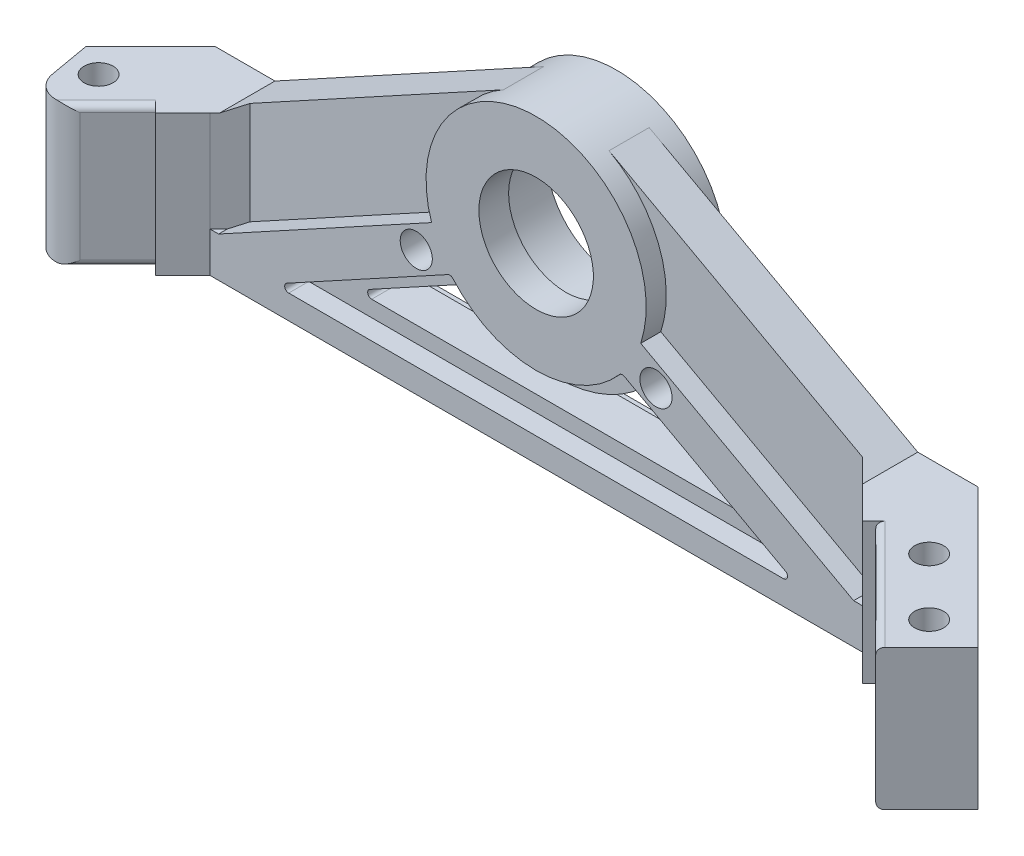
SolidWorks part; units mm, degrees
note: The reader was unsure of these and kept them because the rebuilt part matched: shared geometry of "Sketch2<3>", "Sketch2<5>", "Sketch5<3>".
ref_plane "Front Plane" through (0, 0, 0) normal (0, 0, 1) x (1, 0, 0)
ref_plane "Top Plane" through (0, 0, 0) normal (0, 1, 0) x (1, 0, 0)
ref_plane "Right Plane" through (0, 0, 0) normal (1, 0, 0) x (0, 0, -1)
sketch "Sketch1" plane through (0, 0, 0) normal (0, 1, 0) x (-1, 0, 0)
  line L48 (74.9309, 32.5085) -> (74.2125, 33.2269)
  line L49 (74.2125, 33.2269) -> (56.9345, 15.9489)
  line L50 (57.6529, 15.2305) -> (56.9345, 15.9489)
  line L51 (-56.9345, 15.9489) -> (-74.2125, 33.2269)
  line L52 (-74.2125, 33.2269) -> (-74.9309, 32.5085)
  line L53 (-56.9345, 15.9489) -> (-57.6529, 15.2305)
  line L54 (-65.0167, 7.8667) -> (-61.5144, 4.3644)
  line L55 (-61.5144, 4.3644) -> (-52.3715, 13.5073)
  line L56 (-52.3715, 13.5073) -> (-55.8738, 17.0096)
  line L57 (-55.8738, 17.0096) -> (-65.0167, 7.8667)
  line L58 (55.8738, 17.0096) -> (52.3715, 13.5073)
  line L59 (52.3715, 13.5073) -> (61.5144, 4.3644)
  line L60 (61.5144, 4.3644) -> (65.0167, 7.8667)
  line L61 (65.0167, 7.8667) -> (55.8738, 17.0096)
  line L62 (17.3112, 9.525) -> (13.6482, 9.525)
  line L63 (17.3112, 12.7) -> (-17.3112, 12.7)
  line L64 (-13.6482, 9.525) -> (-17.3112, 9.525)
  line L65 (-17.3112, 3.175) -> (-13.6482, 3.175)
  line L66 (-17.3112, 0) -> (17.3112, 0)
  line L67 (13.6482, 3.175) -> (17.3112, 3.175)
  line L68 (-17.3112, 12.7) -> (-53.1788, 12.7)
  line L69 (-53.1788, 12.7) -> (-50.0038, 9.525)
  line L70 (-50.0038, 9.525) -> (-17.3112, 9.525)
  line L71 (-60.325, 3.175) -> (-57.15, 0)
  line L72 (-57.15, 0) -> (-17.3112, 0)
  line L73 (-17.3112, 3.175) -> (-60.325, 3.175)
  line L74 (17.3112, 9.525) -> (50.0038, 9.525)
  line L75 (50.0038, 9.525) -> (53.1788, 12.7)
  line L76 (53.1788, 12.7) -> (17.3112, 12.7)
  line L77 (57.15, 0) -> (60.325, 3.175)
  line L78 (60.325, 3.175) -> (17.3112, 3.175)
  line L79 (17.3112, 0) -> (57.15, 0)
  line L80 (-74.9309, 32.5085) -> (-82.2947, 25.1447)
  line L81 (-82.2947, 25.1447) -> (-65.0167, 7.8667)
  line L82 (-65.0167, 7.8667) -> (-57.6529, 15.2305)
  line L83 (-60.325, 3.175) -> (-13.6482, 3.175)
  line L84 (-13.6482, 9.525) -> (-50.0038, 9.525)
  line L85 (-50.0038, 9.525) -> (-53.1788, 12.7)
  line L86 (-53.1788, 12.7) -> (-61.5144, 4.3644)
  line L87 (-61.5144, 4.3644) -> (-60.325, 3.175)
  line L88 (13.6482, 3.175) -> (60.325, 3.175)
  line L89 (60.325, 3.175) -> (61.5144, 4.3644)
  line L90 (61.5144, 4.3644) -> (53.1788, 12.7)
  line L91 (53.1788, 12.7) -> (50.0038, 9.525)
  line L92 (50.0038, 9.525) -> (13.6482, 9.525)
  line L93 (82.2947, 25.1447) -> (74.9309, 32.5085)
  line L94 (57.6529, 15.2305) -> (65.0167, 7.8667)
  line L95 (65.0167, 7.8667) -> (82.2947, 25.1447)
sketch "Sketch3" plane through (0, 0, 0) normal (0, 1, 0) x (1, 0, 0)
  line L0 (-53.1788, -12.7) -> (-17.3112, -12.7) construction
  line L1 (-17.3112, 0) -> (-57.15, 0) construction
  line L2 (-57.15, 0) -> (-60.325, -3.175) construction
  line L3 (-60.325, -3.175) -> (-61.5144, -4.3644) construction
  line L4 (-61.5144, -4.3644) -> (-65.0167, -7.8667) construction
  line L5 (-74.2125, -33.2269) -> (-56.9345, -15.9489) construction
  line L6 (-74.9309, -32.5085) -> (-74.2125, -33.2269) construction
  line L7 (-82.2947, -25.1447) -> (-74.9309, -32.5085) construction
  line L8 (-65.0167, -7.8667) -> (-82.2947, -25.1447) construction
  line L9 (-51.5642, -12.7) -> (-17.3112, -12.7)
  line L10 (-17.3112, 0) -> (-57.15, 0)
  line L11 (-57.15, 0) -> (-60.325, -3.175)
  line L12 (-60.325, -3.175) -> (-61.5144, -4.3644)
  line L13 (-61.5144, -4.3644) -> (-65.0167, -7.8667)
  line L14 (-74.2125, -33.2269) -> (-56.9345, -15.9489)
  line L15 (-74.9309, -32.5085) -> (-74.2125, -33.2269)
  line L16 (-82.2947, -25.1447) -> (-74.9309, -32.5085)
  line L17 (-65.0167, -7.8667) -> (-82.2947, -25.1447)
  line L18 (0, 0) -> (0, -12.7) construction
  line L19 (-17.3112, -12.7) -> (17.3112, -12.7) construction
  line L20 (17.3112, 0) -> (-17.3112, 0) construction
  line L21 (-52.3715, -13.5073) -> (-61.5144, -4.3644) construction
  line L22 (-65.0167, -7.8667) -> (-55.8738, -17.0096) construction
  line L23 (-55.8738, -17.0096) -> (-52.3715, -13.5073) construction
  line L24 (17.3112, 0) -> (-17.3112, 0)
  line L25 (-17.3112, -12.7) -> (17.3112, -12.7)
  line L26 (-52.3715, -13.5073) -> (-61.5144, -4.3644)
  line L27 (-65.0167, -7.8667) -> (-55.8738, -17.0096)
  line L28 (-55.8738, -17.0096) -> (-52.3715, -13.5073)
  line L29 (55.8738, -17.0096) -> (52.3715, -13.5073)
  line L30 (65.0167, -7.8667) -> (55.8738, -17.0096)
  line L31 (52.3715, -13.5073) -> (61.5144, -4.3644)
  line L32 (65.0167, -7.8667) -> (82.2947, -25.1447)
  line L33 (82.2947, -25.1447) -> (74.9309, -32.5085)
  line L34 (74.9309, -32.5085) -> (74.2125, -33.2269)
  line L35 (74.2125, -33.2269) -> (56.9345, -15.9489)
  line L36 (61.5144, -4.3644) -> (65.0167, -7.8667)
  line L37 (60.325, -3.175) -> (61.5144, -4.3644)
  line L38 (57.15, 0) -> (60.325, -3.175)
  line L39 (17.3112, 0) -> (57.15, 0)
  line L40 (51.5642, -12.7) -> (17.3112, -12.7)
  line L41 (-52.3715, -13.5073) -> (-51.5642, -12.7)
  line L42 (52.3715, -13.5073) -> (51.5642, -12.7)
extrude "Boss-Extrude1" add sketch "Sketch3" along normal mid plane 22.225 contours L27 L17 L16 L15 L14 | L27 L28 L26 L13 | L18 L24 L10 L11 L12 L26 L41 L9 L25 | L24 L18 L25 L40 L42 L31 L37 L38 L39 | L36 L31 L29 L30 | L35 L34 L33 L32 L30
sketch "Sketch2" plane through (0, 0, 0) normal (0, 0, 1) x (1, 0, 0)
  line L0 (0, 0) -> (0, 36.45) construction
  line L1 (-17.3112, 0) -> (17.3112, 0) construction
  line L2 (50.8048, 11.1125) -> (8.3447, 34.3184)
  line L3 (-50.8048, 11.1125) -> (-8.3447, 34.3184)
  line L4 (50.8048, 11.1125) -> (15.4841, 11.1125)
  line L5 (57.15, 11.1125) -> (-57.15, 11.1125) construction
  line L6 (-50.8048, 11.1125) -> (-15.4841, 11.1125)
  circle A0 centre (0, 19.05) radius 11.05
  circle A1 centre (0, 19.05) radius 17.4
  circle A2 centre (0, 19.05) radius 9.05
  dimension "D1" = 22.1
  dimension "D2" = 6.35
  dimension "D4" = 2
  dimension "D3" = 19.05
extrude "Boss-Extrude2" add sketch "Sketch2" along normal up to surface (12.7 mm away) contours A1 L3 L6 | A1 L0 A0 | A0 L0 | L0 A0 | L0 A1 A0 | A1 L4 L2 | A2
extrude "Cut-Extrude2" cut sketch "Sketch2<3>" along normal blind 8 contours A0 L0 A2 | A2 L0 | L0 A2 | L0 A0 A2
sketch "Sketch2<3>" plane through (0, 0, 0) normal (0, 0, 1) x (1, 0, 0) same geometry as "Sketch2"
extrude "Cut-Extrude3" cut sketch "Sketch2<5>" along normal through all contours A2 L0 | L0 A2
sketch "Sketch2<5>" plane through (0, 0, 0) normal (0, 0, 1) x (1, 0, 0) same geometry as "Sketch2"
sketch "Sketch5" plane through (0, 0, 0) normal (0, 0, -1) x (-1, 0, 0)
  line L0 (-16.5348, 13.6314) -> (-57.15, -8.5663)
  line L1 (-48.5682, -11.1125) -> (-13.4894, 8.0593)
  line L2 (0, 19.05) -> (-55.1885, -11.1125) construction
  line L3 (0, 19.05) -> (0, -11.1125) construction
  line L4 (16.5348, 13.6314) -> (57.15, -8.5663)
  line L5 (48.5682, -11.1125) -> (13.4894, 8.0593)
  line L6 (0, 19.05) -> (55.1885, -11.1125) construction
  line L7 (57.15, 11.1125) -> (50.8048, 11.1125)
  line L8 (50.8048, 11.1125) -> (8.3447, 34.3184)
  line L9 (-8.3447, 34.3184) -> (-50.8048, 11.1125)
  line L10 (-50.8048, 11.1125) -> (-57.15, 11.1125)
  line L11 (-57.15, 11.1125) -> (-57.15, -11.1125)
  line L12 (-57.15, -11.1125) -> (57.15, -11.1125)
  line L13 (57.15, -11.1125) -> (57.15, 11.1125)
  line L14 (57.15, 11.1125) -> (50.8048, 11.1125)
  line L15 (50.8048, 11.1125) -> (8.3447, 34.3184)
  line L16 (-8.3447, 34.3184) -> (-50.8048, 11.1125)
  line L17 (-50.8048, 11.1125) -> (-57.15, 11.1125)
  line L18 (-57.15, 11.1125) -> (-57.15, -11.1125)
  line L19 (-57.15, -11.1125) -> (57.15, -11.1125)
  line L20 (57.15, -11.1125) -> (57.15, 11.1125)
  line L21 (-41.597, -7.3025) -> (41.597, -7.3025)
  line L22 (-31.6533, -4.7625) -> (31.6533, -4.7625)
  line L23 (-31.6533, -4.7625) -> (-14.0224, 4.8734)
  line L24 (31.6533, -4.7625) -> (14.0224, 4.8734)
  line L25 (-57.15, 11.1125) -> (-82.2947, 11.1125)
  line L26 (-82.2947, 11.1125) -> (-82.2947, -11.1125)
  line L27 (-82.2947, -11.1125) -> (-57.15, -11.1125)
  line L28 (-82.2947, -4.7625) -> (-50.1902, -4.7625)
  line L29 (82.2947, -4.7625) -> (50.1902, -4.7625)
  line L33 (57.15, -11.1125) -> (82.2947, -11.1125)
  line L34 (82.2947, -11.1125) -> (82.2947, 11.1125)
  line L35 (82.2947, 11.1125) -> (57.15, 11.1125)
  line L36 (57.15, 11.1125) -> (57.15, -11.1125)
  line L37 (57.15, -11.1125) -> (82.2947, -11.1125)
  line L38 (82.2947, -11.1125) -> (82.2947, 11.1125)
  line L39 (82.2947, 11.1125) -> (57.15, 11.1125)
  line L40 (57.15, 11.1125) -> (57.15, -11.1125)
  circle A0 centre (0, 19.05) radius 11.05 construction
  arc A1 (8.3447, 34.3184) -> (-8.3447, 34.3184) centre (0, 19.05) ccw
  arc A2 (8.3447, 34.3184) -> (-8.3447, 34.3184) centre (0, 19.05) ccw
  circle A3 centre (0, 19.05) radius 11.05
  circle A4 centre (0, 19.05) radius 17.4
  arc A5 (-14.0224, 4.8734) -> (14.0224, 4.8734) centre (0, 19.05) ccw
  circle A6 centre (0, 19.05) radius 19.94 construction
  line M30 (57.15, 11.1125) -> (50.8048, 11.1125)
  line M31 (50.8048, 11.1125) -> (8.3447, 34.3184)
  line M33 (-8.3447, 34.3184) -> (-50.8048, 11.1125)
  line M34 (-50.8048, 11.1125) -> (-57.15, 11.1125)
  line M35 (-57.15, 11.1125) -> (-57.15, -11.1125)
  dimension "D2" = 3.175
  dimension "D3" = 3.175
  dimension "D4" = 3.81
  dimension "D6" = 2.54
  dimension "D7" = 2.54
  dimension "D9" = 6.35
  dimension "D1" = 0
  dimension "D5" = 2.54
  dimension "D8" = 0
extrude "Cut-Extrude4" cut sketch "Sketch5" against normal blind 3.175 contours L26 L28 L25 M35 | A4 L28 L0 M33 M34 M35 | A4 L4 L29 L20 M30 M31 | L38 L39 L20 L29 | A4 L1 L21 L5 L23 A5 L24 L22
extrude "Cut-Extrude5" cut sketch "Sketch5<3>" against normal through all contours A5 L23 L22 L24
sketch "Sketch5<3>" plane through (0, 0, 0) normal (0, 0, -1) x (-1, 0, 0) same geometry as "Sketch5"
sketch "Sketch6" plane through (0, 0, 0) normal (0, 0, -1) x (-1, 0, 0)
  line L0 (0, 19.05) -> (-18.9451, 8.6958) construction
  line L1 (-16.5348, 13.6314) -> (-50.1902, -4.7625) construction
  line L2 (0, 19.05) -> (0, 0) construction
  circle A0 centre (0, 19.05) radius 11.05 construction
  circle A1 centre (0, 19.05) radius 11.05 construction
  circle A2 centre (-18.9451, 8.6958) radius 2.54
  circle A3 centre (18.9451, 8.6958) radius 2.54
  dimension "D2" = 5.08
  dimension "D1" = 21.59
extrude "Cut-Extrude6" cut sketch "Sketch6" against normal through all contours A2 | A3
sketch "Sketch7" plane through (0, 0, 12.7) normal (0, 0, 1) x (1, 0, 0)
  line L0 (0, 19.05) -> (-51.5642, -9.1317) construction
  line L1 (0, 19.05) -> (0, 0) construction
  line L2 (0, 19.05) -> (51.5642, -9.1317) construction
  line L3 (-51.5642, -5.5134) -> (-8.9593, 17.7717)
  line L4 (-50.1902, -4.7625) -> (-51.5642, -4.7625)
  line L5 (-48.5189, -11.0856) -> (-5.9139, 12.1996)
  line L6 (48.5189, -11.0856) -> (5.9139, 12.1996)
  line L7 (51.5642, 11.1125) -> (50.8048, 11.1125)
  line L8 (50.8048, 11.1125) -> (8.3447, 34.3184)
  line L9 (-8.3447, 34.3184) -> (-50.8048, 11.1125)
  line L10 (-50.8048, 11.1125) -> (-51.5642, 11.1125)
  line L11 (-51.5642, 11.1125) -> (-51.5642, -11.1125)
  line L12 (-51.5642, -11.1125) -> (51.5642, -11.1125)
  line L13 (51.5642, -11.1125) -> (51.5642, 11.1125)
  line L14 (51.5642, 11.1125) -> (50.8048, 11.1125)
  line L15 (50.8048, 11.1125) -> (8.3447, 34.3184)
  line L16 (-8.3447, 34.3184) -> (-50.8048, 11.1125)
  line L17 (-50.8048, 11.1125) -> (-51.5642, 11.1125)
  line L18 (-51.5642, 11.1125) -> (-51.5642, -11.1125)
  line L19 (-51.5642, -11.1125) -> (51.5642, -11.1125)
  line L20 (51.5642, -11.1125) -> (51.5642, 11.1125)
  line L21 (50.1902, -4.7625) -> (51.5642, -4.7625)
  line L22 (51.5642, -5.5134) -> (8.9593, 17.7717)
  line L23 (-41.597, -7.3025) -> (41.597, -7.3025)
  circle A0 centre (0, 19.05) radius 9.05 construction
  arc A1 (8.3447, 34.3184) -> (-8.3447, 34.3184) centre (0, 19.05) ccw
  arc A2 (8.3447, 34.3184) -> (-8.3447, 34.3184) centre (0, 19.05) ccw
  circle A3 centre (0, 19.05) radius 9.05
  circle A4 centre (0, 19.05) radius 9.05
  circle A8 centre (0, 19.05) radius 17.4
  dimension "D2" = 6.35
  dimension "D3" = 6.35
  dimension "D4" = 3.81
  dimension "D1" = 0
extrude "Cut-Extrude7" cut sketch "Sketch7" against normal blind 3.175
chamfer "Chamfer1" distance 3.175 angle 45 10 edges at (51.1845, 11.1125, 9.525) (51.5642, 3.175, 9.525) (51.5642, 11.1125, 11.1125) (50.8772, -4.7625, 9.525) (51.5642, -4.7625, 11.1125) (-51.5642, 3.175, 9.525) (-51.5642, -4.7625, 11.1125) (-51.1845, 11.1125, 9.525) (-51.5642, 11.1125, 11.1125) (-50.8772, -4.7625, 9.525)
fillet "Fillet1" radius 0.635 12 edges at (-41.597, -7.3025, 1.5875) (41.597, -7.3025, 1.5875) (13.4894, 8.0593, 1.5875) (-13.4894, 8.0593, 1.5875) (14.0224, 4.8734, 6.35) (-14.0224, 4.8734, 6.35) (-31.6533, -4.7625, 6.35) (31.6533, -4.7625, 6.35) (41.597, -7.3025, 11.1125) (-41.597, -7.3025, 11.1125) (13.4894, 8.0593, 11.1125) (-13.4894, 8.0593, 11.1125)
fillet "Fillet3" radius 1.016 4 edges at (65.5735, -11.1125, 24.5879) (-65.5735, -11.1125, 24.5879) (65.5735, 11.1125, 24.5879) (-65.5735, 11.1125, 24.5879)
sketch "Sketch8" plane through (0, 11.1125, 0) normal (0, 1, 0) x (1, 0, 0)
  line L0 (57.6529, -15.2305) -> (55.8738, -17.0096) construction
  line L1 (57.6529, -15.2305) -> (55.8738, -17.0096)
  line L2 (0, 0) -> (0, -12.7) construction
  line L3 (17.4, 0) -> (-17.4, 0) construction
  line L4 (-17.4, -12.7) -> (17.4, -12.7) construction
  line L5 (57.6529, -15.2305) -> (65.0167, -7.8667)
  line L6 (60.325, -3.175) -> (82.2947, -25.1447) construction
  line L7 (61.1552, -11.7282) -> (78.4332, -29.0062) construction
  line L8 (82.2947, -25.1447) -> (74.9309, -32.5085) construction
  line L10 (-57.6529, -15.2305) -> (-55.8738, -17.0096)
  line L11 (-57.6529, -15.2305) -> (-65.0167, -7.8667)
  line L12 (-61.1552, -11.7282) -> (-78.4332, -29.0062) construction
  circle A0 centre (65.6453, -16.2183) radius 2.286
  circle A1 centre (74.6256, -25.1986) radius 2.286
  circle A2 centre (-65.6453, -16.2183) radius 2.286
  circle A3 centre (-74.6256, -25.1986) radius 2.286
  dimension "D2" = 4.572
  dimension "D3" = 4.572
  dimension "D1" = 5.461
  dimension "D4" = 6.35
  dimension "D5" = 12.7
extrude "Cut-Extrude8" cut sketch "Sketch8" against normal through all contours A1 | A3 | A0 | A2
sketch "Sketch9" plane through (0, 11.1125, 0) normal (0, 1, 0) x (1, 0, 0)
  line L0 (0, 0) -> (0, -12.7) construction
  line L1 (17.4, 0) -> (-17.4, 0) construction
  line L2 (-17.4, -12.7) -> (17.4, -12.7) construction
  line L3 (70.485, -13.335) -> (68.2774, -25.855)
  line L4 (60.325, -3.175) -> (82.2947, -25.1447) construction
  line L5 (57.6529, -15.2305) -> (74.9309, -32.5085) construction
  line L6 (68.2774, -25.855) -> (66.2944, -37.1008)
  line L7 (66.2944, -37.1008) -> (87.3871, -37.1008)
  line L8 (87.3871, -37.1008) -> (87.3871, -13.335)
  line L9 (87.3871, -13.335) -> (70.485, -13.335)
  line L10 (-87.3871, -37.1008) -> (-87.3871, -13.335)
  line L11 (-66.2944, -37.1008) -> (-87.3871, -37.1008)
  line L12 (-68.2774, -25.855) -> (-66.2944, -37.1008)
  line L13 (-70.485, -13.335) -> (-68.2774, -25.855)
  line L14 (-87.3871, -13.335) -> (-70.485, -13.335)
  dimension "D1" = 13.335
  dimension "D2" = 100
extrude "Cut-Extrude9" cut sketch "Sketch9" against normal through all and the other way through all contours L10 L14 L13 L12 L11
fillet "Fillet4" radius 3.81 1 edges at (-68.062, 0, 27.0765)
sketch "Sketch11" plane through (0, -11.1125, 0) normal (0, -1, 0) x (1, 0, 0)
  line L0 (0, 0) -> (0, 12.7) construction
  line L1 (57.15, 0) -> (-57.15, 0) construction
  line L2 (-51.5642, 12.7) -> (51.5642, 12.7) construction
  line L3 (63.5, 6.35) -> (-63.5, 6.35) construction
  line L4 (-57.15, 0) -> (-70.485, 13.335) construction
  text T0 "<b>SN102</b>"
  point P11 (0, 6.35)
extrude "Cut-Extrude10" cut sketch "Sketch11" against normal blind 0.5
